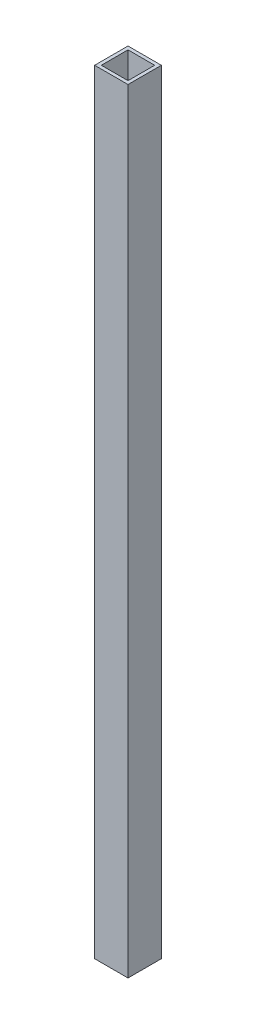
SolidWorks part; units mm, degrees
material "6061 Alloy"
ref_plane "Front Plane" through (0, 0, 0) normal (0, 0, 1) x (1, 0, 0)
ref_plane "Top Plane" through (0, 0, 0) normal (0, 1, 0) x (1, 0, 0)
ref_plane "Right Plane" through (0, 0, 0) normal (1, 0, 0) x (0, 0, -1)
sketch "Sketch1" plane through (0, 0, 0) normal (0, 1, 0) x (1, 0, 0)
  line L1 (0, 0) -> (15, 0)
  line L2 (0, 0) -> (0, 15)
  line L3 (0, 15) -> (15, 15)
  line L4 (15, 0) -> (15, 15)
  dimension "D1" = 15
extrude "Extrude-Thin1" add sketch "Sketch1" along normal blind 348 thin thin type one direction reverse wall 1.5
